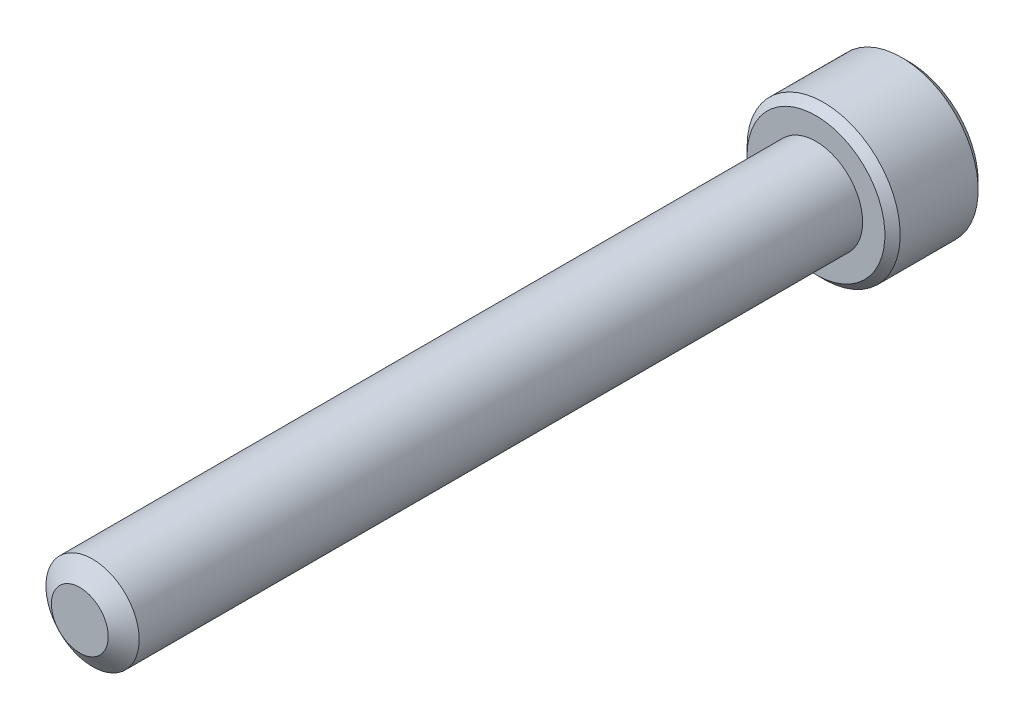
SolidWorks part; units mm, degrees
ref_plane "Front Plane" through (0, 0, 0) normal (0, 0, 1) x (1, 0, 0)
ref_plane "Top Plane" through (0, 0, 0) normal (0, 1, 0) x (1, 0, 0)
ref_plane "Right Plane" through (0, 0, 0) normal (1, 0, 0) x (0, 0, -1)
sketch "Sketch1" plane through (0, 0, 0) normal (0, 0, 1) x (1, 0, 0)
  circle A0 centre (0, 0) radius 2.413
  dimension "OD" = 4.826
extrude "Extrude1" add sketch "Sketch1" against normal blind 38.1
sketch "Sketch2" plane through (0, 0, 0) normal (0, 0, 1) x (1, 0, 0)
  circle A0 centre (0, 0) radius 2.413 construction
  circle A1 centre (0, 0) radius 2.413
curve "Helix/Spiral1" pitch 1.0583 height 39.1583 turns 37 parameters "pitch"=1.0583
sketch "Sketch3" plane through (0, 0, 0) normal (1, 0, 0) x (0, 0, -1)
  line L0 (-0.926, 2.413) -> (-0.5292, 1.7256)
  line L1 (-0.5292, 1.7256) -> (-0.3969, 1.7256)
  line L2 (-0.3969, 1.7256) -> (0, 2.413)
  line L3 (-0.926, 2.413) -> (0, 2.413)
  line L4 (-0.463, 2.413) -> (-0.463, 1.7256) construction
  line L5 (-0.7276, 2.0693) -> (-0.1984, 2.0693) construction
  line L6 (0, 2.413) -> (0, -2.413) construction
  dimension "D1" = 0.1323
  dimension "D2" = 0.5292
  dimension "D3" = 60
sweep "Cut-Sweep1" [suppressed] cut profiles "Sketch3" path "Helix/Spiral1"
sketch "Sketch4" plane through (0, 0, 0) normal (1, 0, 0) x (0, 0, -1)
  line L0 (0.6592, 2.413) -> (0, 1.4716)
  line L1 (0, 1.4716) -> (0, 2.413)
  line L2 (0.6592, 2.413) -> (0, 2.413)
  line L3 (-0.926, 2.413) -> (0, 2.413) construction
  line L4 (0, 0) -> (7.0209, 0) construction
  dimension "D1" = 55
  dimension "D2" = 0.254
revolve "Cut-Revolve1" cut sketch "Sketch4" angle 360 about L4
sketch "Sketch6" plane through (0, 0, -38.1) normal (0, 0, -1) x (-1, 0, 0)
  circle A0 centre (0, 0) radius 3.9624
  dimension "head dia" = 7.9248
extrude "Extrude2" add sketch "Sketch6" along normal blind 4.826
sketch "Sketch7" plane through (0, 0, -42.926) normal (0, 0, -1) x (-1, 0, 0)
  line L1 (0, 2.2914) -> (-1.9844, 1.1457)
  line L2 (-1.9844, 1.1457) -> (-1.9844, -1.1457)
  line L3 (-1.9844, -1.1457) -> (0, -2.2914)
  line L4 (0, -2.2914) -> (1.9844, -1.1457)
  line L5 (1.9844, -1.1457) -> (1.9844, 1.1457)
  line L6 (1.9844, 1.1457) -> (0, 2.2914)
  circle A0 centre (0, 0) radius 1.9844 construction
  dimension "hex dia" = 3.9688
extrude "Cut-Extrude1" cut sketch "Sketch7" against normal blind 2.9766
sketch "Sketch8" plane through (0, 0, -42.926) normal (0, 0, -1) x (-1, 0, 0)
  circle A0 centre (0, 0) radius 2.2914
extrude "Cut-Extrude2" cut sketch "Sketch8" against normal through all draft 45
chamfer "Chamfer1" distance 0.3962 angle 45 2 edges at (-3.9624, 0, -42.926) (-3.9624, 0, -38.1)
sketch "Sketch10" plane through (0, 0, -38.1) normal (0, 0, 1) x (1, 0, 0)
  circle A0 centre (0, 0) radius 2.413
extrude "Partial Thread" [suppressed] add sketch "Sketch10" along normal offset from surface (19.05 mm away) 2.54 up to face at (1.4716, 0, 0)
sketch "Sketch9" plane through (0, 0, 0) normal (1, 0, 0) x (0, 0, -1)
  line L0 (0, 2.413) -> (0, -2.413) construction
  line L1 (1.5875, 2.413) -> (1.5875, -2.413) construction
  dimension "D1" = 1.5875
equation "\"D3@Helix/Spiral1\" = \"screw length@Extrude1\"+\"pitch@Helix/Spiral1\""
equation "\"D1@Sketch3\" = \"pitch@Helix/Spiral1\"*.125"
equation "\"D2@Sketch3\" = \"pitch@Helix/Spiral1\"*.5"
equation "\"D1@Cut-Extrude1\" = \"hex dia@Sketch7\"*.75"
equation "\"D1@Chamfer1\" = \"head dia@Sketch6\"*.05"
equation "\"D1@Sketch9\" = \"pitch@Helix/Spiral1\"*1.5"
